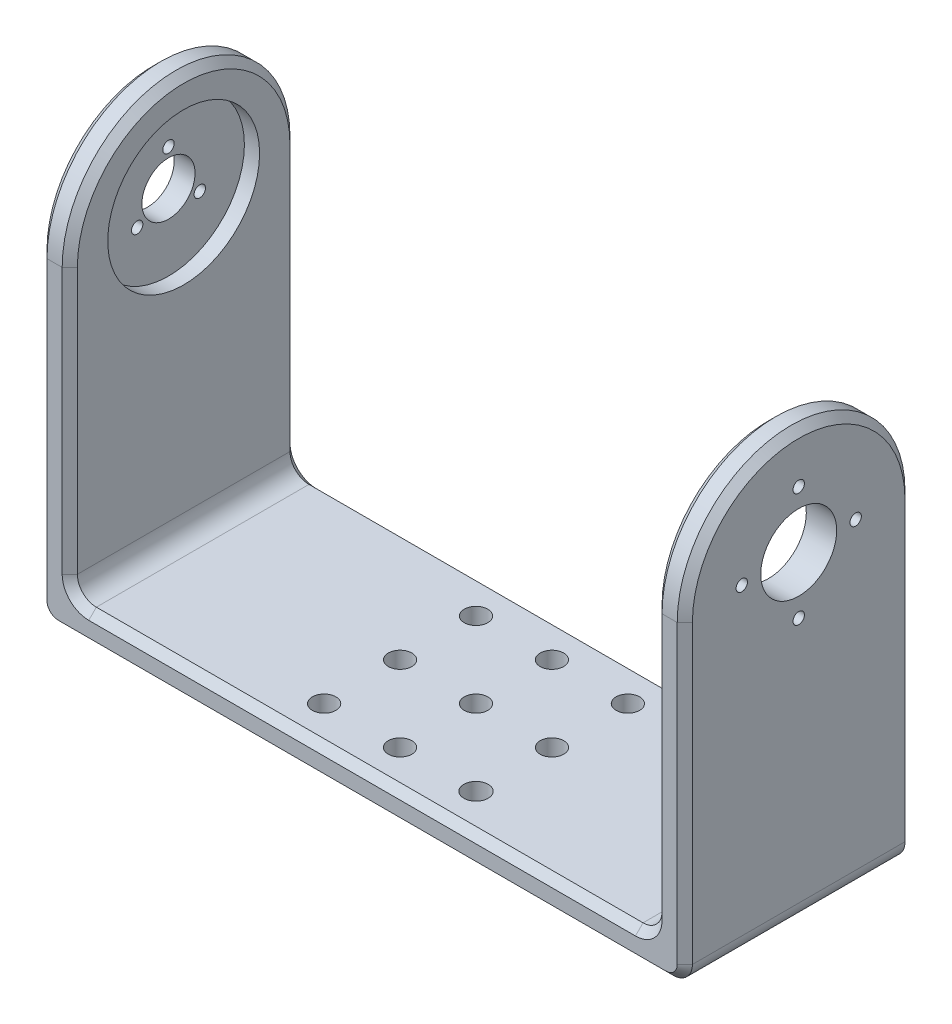
SolidWorks part; units mm, degrees
ref_plane "Front Plane" through (0, 0, 0) normal (0, 0, 1) x (1, 0, 0)
ref_plane "Top Plane" through (0, 0, 0) normal (0, 1, 0) x (1, 0, 0)
ref_plane "Right Plane" through (0, 0, 0) normal (1, 0, 0) x (0, 0, -1)
sketch "Sketch1" plane through (0, 0, 0) normal (0, 1, 0) x (1, 0, 0)
  line L1 (-85, 30) -> (85, 30)
  line L2 (-85, 30) -> (-85, -30)
  line L3 (-85, -30) -> (85, -30)
  line L4 (85, 30) -> (85, -30)
extrude "Boss-Extrude1" add sketch "Sketch1" along normal blind 8
sketch "Sketch2" plane through (0, 8, 0) normal (0, 1, 0) x (1, 0, 0)
  line L1 (-85, 30) -> (-77, 30)
  line L2 (-85, 30) -> (-85, -30)
  line L3 (-85, -30) -> (-77, -30)
  line L4 (-77, 30) -> (-77, -30)
  line L5 (77, 30) -> (77, -30)
  line L6 (85, -30) -> (77, -30)
  line L7 (85, 30) -> (85, -30)
  line L8 (85, 30) -> (77, 30)
extrude "Boss-Extrude2" add sketch "Sketch2" along normal blind 105
sketch "Sketch3" plane through (85, 0, 0) normal (1, 0, 0) x (0, 0, -1)
  circle A0 centre (0, 85) radius 10
  circle A3 centre (0, 70) radius 1.5
  circle A4 centre (0, 100) radius 1.5
  circle A5 centre (-15, 85) radius 1.5
  circle A6 centre (15, 85) radius 1.5
extrude "Cut-Extrude1" cut sketch "Sketch3" against normal blind 10
sketch "Sketch5" plane through (-85, 0, 0) normal (-1, 0, 0) x (0, 0, 1)
  circle A0 centre (0, 85) radius 15
extrude "Boss-Extrude3" add sketch "Sketch5" along normal blind 1.5
sketch "Sketch6" plane through (-86.5, 0, 0) normal (-1, 0, 0) x (0, 0, 1)
  circle A0 centre (0, 85) radius 7
extrude "Cut-Extrude3" cut sketch "Sketch6" against normal blind 15
sketch "Sketch7" plane through (-77, 0, 0) normal (1, 0, 0) x (0, 0, -1)
  circle A0 centre (0, 85) radius 20
extrude "Cut-Extrude4" cut sketch "Sketch7" against normal blind 4
fillet "Fillet1" 2 edges at (81, 113, -30) (81, 113, 30) type full round first side face at (0, 58.5, -30) second side face at (0, 58.5, 30) middle face at (81, 113, 0)
fillet "Fillet2" 2 edges at (-81, 113, -30) (-81, 113, 30) type full round first side face at (0, 51, -30) second side face at (0, 51, 30) middle face at (-81, 113, 0)
fillet "Fillet3" radius 5 1 edges at (77, 8, 0) type face fillet first side face at (77, 70, -1.5) second side face at (0, 8, 0)
fillet "Fillet4" radius 5 1 edges at (-77, 8, 0) type face fillet first side face at (-77, 85, -20) second side face at (-2.5, 8, 0)
fillet "Fillet5" radius 5 1 edges at (85, 0, 0) type face fillet first side face at (85, 70, -1.5) second side face at (0, 0, 0)
fillet "Fillet6" radius 5 1 edges at (-85, 0, 0) type face fillet first side face at (-85, 85, -15) second side face at (-2.5, 0, 0)
fillet "Chamfer1" radius 2 24 edges at (85, 113, 0) (77, 113, 0) (-77, 113, 0) (-85, 113, 0) (83.5355, 1.4645, -30) (85, 44, -30) (77, 48, -30) (75.5355, 9.4645, -30) (0, 8, -30) (-75.5355, 9.4645, -30) (-77, 48, -30) (-85, 44, -30) (-83.5355, 1.4645, -30) (-77, 48, 30) (-75.5355, 9.4645, 30) (0, 8, 30) (75.5355, 9.4645, 30) (77, 48, 30) (85, 44, 30) (83.5355, 1.4645, 30) (-83.5355, 1.4645, 30) (-85, 44, 30) (0, 0, -30) (0, 0, 30) profile chamfer
sketch "Sketch8" plane through (0, 8, 0) normal (0, 1, 0) x (1, 0, 0)
  circle A0 centre (0, 0) radius 3.1
  circle A1 centre (0, 20) radius 3.1
  circle A2 centre (0, -20) radius 3.1
  circle A3 centre (-20, -20) radius 3.1
  circle A4 centre (-20, 20) radius 3.1
  circle A5 centre (-20, 0) radius 3.1
  circle A6 centre (20, -20) radius 3.2
  circle A7 centre (20, 0) radius 3.1
  circle A8 centre (20, 20) radius 3.1
extrude "Cut-Extrude5" cut sketch "Sketch8" against normal blind 10
sketch "Sketch10" plane through (-81, 0, 0) normal (1, 0, 0) x (0, 0, -1)
  circle A1 centre (0, 94.525) radius 1.5
  circle A2 centre (8.2489, 80.2375) radius 1.5
  circle A3 centre (-8.2489, 80.2375) radius 1.5
  point P10 (0, 85)
  dimension "D1" = 3
extrude "Cut-Extrude7" cut sketch "Sketch10" against normal blind 10
